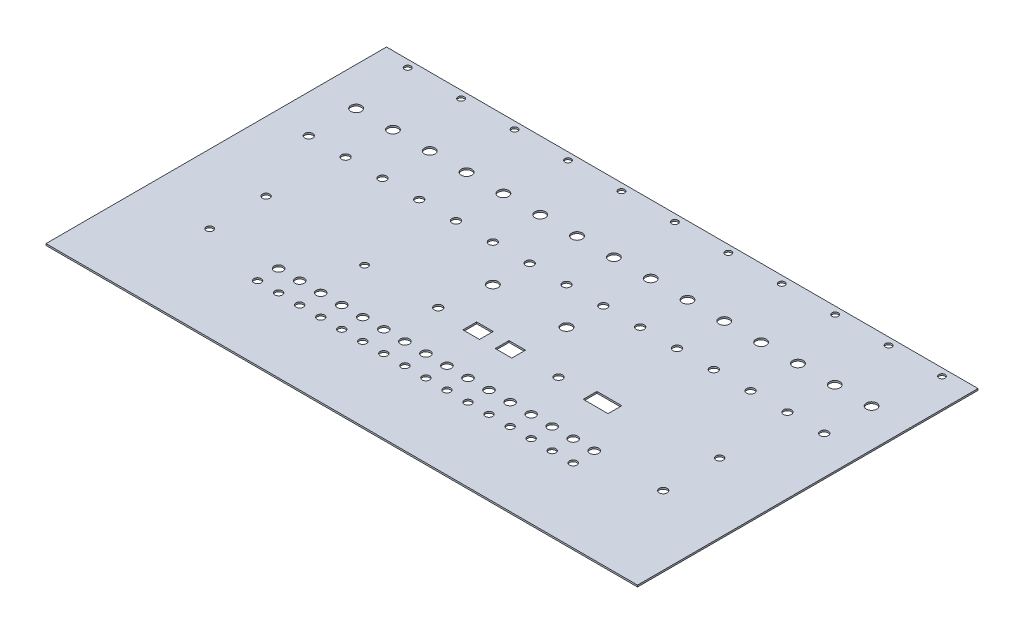
SolidWorks part; units mm, degrees
ref_plane "Front Plane" through (0, 0, 0) normal (0, 0, 1) x (1, 0, 0)
ref_plane "Top Plane" through (0, 0, 0) normal (0, 1, 0) x (1, 0, 0)
ref_plane "Right Plane" through (0, 0, 0) normal (1, 0, 0) x (0, 0, -1)
sketch "Sketch1" plane through (0, 0, 0) normal (0, 1, 0) x (1, 0, 0)
  line L1 (281.15, -161.825) -> (-281.15, -161.825)
  line L2 (281.15, -161.825) -> (281.15, 161.825)
  line L3 (281.15, 161.825) -> (-281.15, 161.825)
  line L4 (-281.15, -161.825) -> (-281.15, 161.825)
  line L5 (281.15, -161.825) -> (-281.15, 161.825) construction
  line L6 (281.15, 161.825) -> (-281.15, -161.825) construction
  point P0 (0, 0)
  dimension "D1" = 323.65
  dimension "D2" = 562.3
extrude "Boss-Extrude1" add sketch "Sketch1" along normal blind 1.5875
sketch "Sketch6" plane through (0, 1.5875, 0) normal (0, 1, 0) x (1, 0, 0)
  line L0 (-281.15, 161.825) -> (-281.15, -161.825) construction
  line L1 (-281.15, -161.825) -> (281.15, -161.825) construction
  circle A0 centre (-150, -91.825) radius 3.5
  dimension "D1" = 131.15
  dimension "D2" = 70
extrude "Cut-Extrude2" cut sketch "Sketch6" against normal up to next
pattern_linear "LPattern2" count 16 spacing 20 along (1, 0, 0) of "Cut-Extrude2"
sketch "Sketch7" plane through (0, 1.5875, 0) normal (0, 1, 0) x (1, 0, 0)
  line L0 (-281.15, 161.825) -> (-281.15, -161.825) construction
  circle A0 centre (-150, -71.825) radius 4.25
  circle A1 centre (-150, -91.825) radius 3.5 construction
  dimension "D1" = 131.15
  dimension "D3" = 8.5
  dimension "D2" = 20
extrude "Cut-Extrude3" cut sketch "Sketch7" against normal up to next
pattern_linear "LPattern3" count 16 spacing 20 along (1, 0, 0) of "Cut-Extrude3"
sketch "Sketch8" plane through (0, 1.5875, 0) normal (0, 1, 0) x (1, 0, 0)
  line L1 (-281.15, 161.825) -> (-281.15, -161.825) construction
  line L2 (-281.15, -161.825) -> (281.15, -161.825) construction
  circle A0 centre (-215.575, -71.825) radius 3.3
  dimension "D1" = 90
  dimension "D2" = 65.575
extrude "Cut-Extrude4" cut sketch "Sketch8" against normal up to next
sketch "Sketch12" plane through (0, 1.5875, 0) normal (0, 1, 0) x (1, 0, 0)
  text T0 "BPM Control\r\n\r\n"
sketch "Sketch13" plane through (0, 1.5875, 0) normal (0, 1, 0) x (1, 0, 0)
  text T0 "Channel Select"
sketch "Sketch14" plane through (0, 1.5875, 0) normal (0, 1, 0) x (1, 0, 0)
  text T0 "Master Volume\r\n"
sketch "Sketch15" plane through (0, 1.5875, 0) normal (0, 1, 0) x (1, 0, 0)
  line L0 (281.15, 161.825) -> (-281.15, 161.825) construction
  line L1 (126.0074, -34.715) -> (102.3974, -34.715)
  line L2 (126.0074, -34.715) -> (126.0074, -21.635)
  line L3 (126.0074, -21.635) -> (102.3974, -21.635)
  line L4 (102.3974, -34.715) -> (102.3974, -21.635)
  line L5 (126.0074, -34.715) -> (102.3974, -21.635) construction
  line L6 (126.0074, -21.635) -> (102.3974, -34.715) construction
  point P0 (114.2024, -28.175)
  dimension "D1" = 13.08
  dimension "D2" = 23.61
  dimension "D3" = 190
extrude "Cut-Extrude7" cut sketch "Sketch15" against normal up to next
sketch "Sketch16" plane through (0, 1.5875, 0) normal (0, 1, 0) x (1, 0, 0)
  line L0 (281.15, 161.825) -> (-281.15, 161.825) construction
  circle A0 centre (-41.9525, -28.175) radius 3.8
  dimension "D1" = 190
  dimension "D2" = 7.6
extrude "Cut-Extrude8" cut sketch "Sketch16" against normal up to next contours A0
sketch "Sketch17" plane through (0, 1.5875, 0) normal (0, 1, 0) x (1, 0, 0)
  text T0 "Loop Back Control\r\n"
sketch "Sketch18" plane through (0, 1.5875, 0) normal (0, 1, 0) x (1, 0, 0)
  line L0 (102.3974, -34.715) -> (126.0074, -34.715) construction
  line L1 (3.7875, -34.715) -> (-11.9525, -34.715)
  line L2 (3.7875, -34.715) -> (3.7875, -21.635)
  line L3 (3.7875, -21.635) -> (-11.9525, -21.635)
  line L4 (-11.9525, -34.715) -> (-11.9525, -21.635)
  line L5 (3.7875, -34.715) -> (-11.9525, -21.635) construction
  line L6 (3.7875, -21.635) -> (-11.9525, -34.715) construction
  point P0 (-4.0825, -28.175)
  dimension "D1" = 13.08
  dimension "D2" = 15.74
  dimension "D3" = 0
extrude "Cut-Extrude9" cut sketch "Sketch18" against normal up to next
sketch "Sketch19" plane through (0, 1.5875, 0) normal (0, 1, 0) x (1, 0, 0)
  line L1 (34.5275, -34.715) -> (18.7875, -34.715)
  line L2 (34.5275, -34.715) -> (34.5275, -21.635)
  line L3 (34.5275, -21.635) -> (18.7875, -21.635)
  line L4 (18.7875, -34.715) -> (18.7875, -21.635)
  line L5 (34.5275, -34.715) -> (18.7875, -21.635) construction
  line L6 (34.5275, -21.635) -> (18.7875, -34.715) construction
  line L7 (-11.9525, -34.715) -> (3.7875, -34.715) construction
  line L8 (3.7875, -34.715) -> (3.7875, -21.635) construction
  point P0 (26.6575, -28.175)
  dimension "D4" = 15
  dimension "D1" = 13.08
  dimension "D2" = 15.74
  dimension "D3" = 0
extrude "Cut-Extrude10" cut sketch "Sketch19" against normal up to next
sketch "Sketch20" plane through (0, 1.5875, 0) normal (0, 1, 0) x (1, 0, 0)
  text T0 "Loop Back"
sketch "Sketch21" plane through (0, 1.5875, 0) normal (0, 1, 0) x (1, 0, 0)
  text T0 "Current Position"
sketch "Sketch23" plane through (0, 1.5875, 0) normal (0, 1, 0) x (1, 0, 0)
  text T0 "Measure Select"
sketch "Sketch24" plane through (0, 1.5875, 0) normal (0, 1, 0) x (1, 0, 0)
  line L0 (-281.15, 161.825) -> (-281.15, -161.825) construction
  line L1 (281.15, 161.825) -> (-281.15, 161.825) construction
  circle A0 centre (-215.57, -18.175) radius 3.5
  text T0 "Start/Stop"
  dimension "D1" = 65.58
  dimension "D2" = 180
extrude "Cut-Extrude12" cut sketch "Sketch24" against normal up to next contours A0
sketch "Sketch25" plane through (0, 1.5875, 0) normal (0, 1, 0) x (1, 0, 0)
  text T0 "Start/Stop\r\n"
sketch "Sketch26" plane through (0, 1.5875, 0) normal (0, 1, 0) x (1, 0, 0)
  line L0 (281.15, -161.825) -> (281.15, 161.825) construction
  line L1 (281.15, 161.825) -> (-281.15, 161.825) construction
  circle A0 centre (215.57, -18.175) radius 3.5
  dimension "D1" = 65.58
  dimension "D2" = 180
extrude "Cut-Extrude13" cut sketch "Sketch26" against normal up to next
sketch "Sketch27" plane through (0, 1.5875, 0) normal (0, 1, 0) x (1, 0, 0)
  text T0 "Reset"
hole_wizard "M7 Clearance Hole1" positions "Sketch30" profile "Sketch31" hole size "M7" standard "ANSI Metric" end condition through all
sketch "Sketch30" plane through (0, 1.5875, 0) normal (0, 1, 0) x (1, 0, 0)
  line L0 (-281.15, 161.825) -> (-281.15, -161.825) construction
  line L1 (281.15, 161.825) -> (-281.15, 161.825) construction
  point P0 (-245, 51.825)
  dimension "D1" = 36.15
  dimension "D2" = 110
sketch "Sketch31" plane through (-245, 1.5875, -51.825) normal (1, 0, 0) x (0, 0, 1)
  line L0 (0, 0) -> (0, 1.5875)
  line L1 (0, 1.5875) -> (3.8, 1.5875)
  line L2 (3.8, 1.5875) -> (3.8, 0)
  line L5 (3.8, 0) -> (0, 0)
  line L11 (0, -6.35) -> (0, 107.95) construction
  dimension "Thru Hole Dia." = 7.6
  dimension "Thru Hole Depth" = 1.5875
pattern_linear "LPattern4" count 15 spacing 35 along (1, 0, 0) of "M7 Clearance Hole1"
sketch "Sketch33" plane through (0, 1.5875, 0) normal (0, 1, 0) x (1, 0, 0)
  circle A0 centre (-245, 96.825) radius 5
  circle A1 centre (-245, 51.825) radius 3.8 construction
  dimension "D1" = 45
  dimension "D2" = 0
extrude "Cut-Extrude14" cut sketch "Sketch33" against normal up to next
pattern_linear "LPattern5" count 15 spacing 35 along (1, 0, 0) of "Cut-Extrude14"
sketch "Sketch34" plane through (0, 1.5875, 0) normal (0, 1, 0) x (1, 0, 0)
  circle A0 centre (-35, 16.825) radius 5
  circle A1 centre (-35, 51.825) radius 3.8 construction
  circle A2 centre (-70, 51.825) radius 3.8 construction
  dimension "D1" = 35
  dimension "D2" = 35
extrude "Cut-Extrude15" cut sketch "Sketch34" against normal up to next
pattern_linear "LPattern6" count 2 spacing 70 along (1, 0, 0) of "Cut-Extrude15"
hole_wizard "M7 Clearance Hole3" positions "Sketch37" profile "Sketch38" hole size "M7" standard "ANSI Metric" end condition through all
sketch "Sketch37" plane through (0, 1.5875, 0) normal (0, 1, 0) x (1, 0, 0)
  line L0 (102.3974, -21.635) -> (102.3974, -34.715) construction
  line L2 (126.0074, -21.635) -> (102.3974, -21.635) construction
  point P0 (72.3974, -28.165)
  point P5 (102.3974, -28.175)
  dimension "D1" = 30
  dimension "D2" = 6.53
sketch "Sketch38" plane through (72.3974, 1.5875, 28.165) normal (1, 0, 0) x (0, 0, 1)
  line L0 (0, 0) -> (0, 1.5875)
  line L1 (0, 1.5875) -> (3.8, 1.5875)
  line L2 (3.8, 1.5875) -> (3.8, 0)
  line L5 (3.8, 0) -> (0, 0)
  line L11 (0, -6.35) -> (0, 107.95) construction
  dimension "Thru Hole Dia." = 7.6
  dimension "Thru Hole Depth" = 1.5875
hole_wizard "M7 Clearance Hole5" positions "Sketch41" profile "Sketch42" hole size "M7" standard "ANSI Metric" end condition through all
sketch "Sketch41" plane through (0, 1.5875, 0) normal (0, 1, 0) x (1, 0, 0)
  line L0 (-281.15, -161.825) -> (281.15, -161.825) construction
  line L1 (281.15, -161.825) -> (281.15, 161.825) construction
  point P0 (215.57, -71.825)
  dimension "D1" = 90
  dimension "D2" = 65.58
sketch "Sketch42" plane through (215.57, 1.5875, 71.825) normal (1, 0, 0) x (0, 0, 1)
  line L0 (0, 0) -> (0, 1.5875)
  line L1 (0, 1.5875) -> (3.8, 1.5875)
  line L2 (3.8, 1.5875) -> (3.8, 0)
  line L5 (3.8, 0) -> (0, 0)
  line L11 (0, -6.35) -> (0, 107.95) construction
  dimension "Thru Hole Dia." = 7.6
  dimension "Thru Hole Depth" = 1.5875
sketch "Sketch43" plane through (0, 1.5875, 0) normal (0, 1, 0) x (1, 0, 0)
  line L0 (-281.15, 161.825) -> (-281.15, -161.825) construction
  line L1 (281.15, 161.825) -> (-281.15, 161.825) construction
  circle A0 centre (-254, 154.825) radius 3
  dimension "D1" = 27.15
  dimension "D2" = 7
extrude "Cut-Extrude16" cut sketch "Sketch43" against normal up to next
pattern_linear "LPattern7" count 11 spacing 50.8 along (1, 0, 0) of "Cut-Extrude16"
sketch "Sketch44" plane through (0, 1.5875, 0) normal (0, 1, 0) x (1, 0, 0)
  line L0 (281.15, 161.825) -> (-281.15, 161.825) construction
  circle A0 centre (-111.9525, -28.175) radius 3.3
  circle A1 centre (-41.9525, -28.175) radius 3.8 construction
  dimension "D1" = 70
  dimension "D2" = 190
extrude "Cut-Extrude17" cut sketch "Sketch44" against normal up to next
